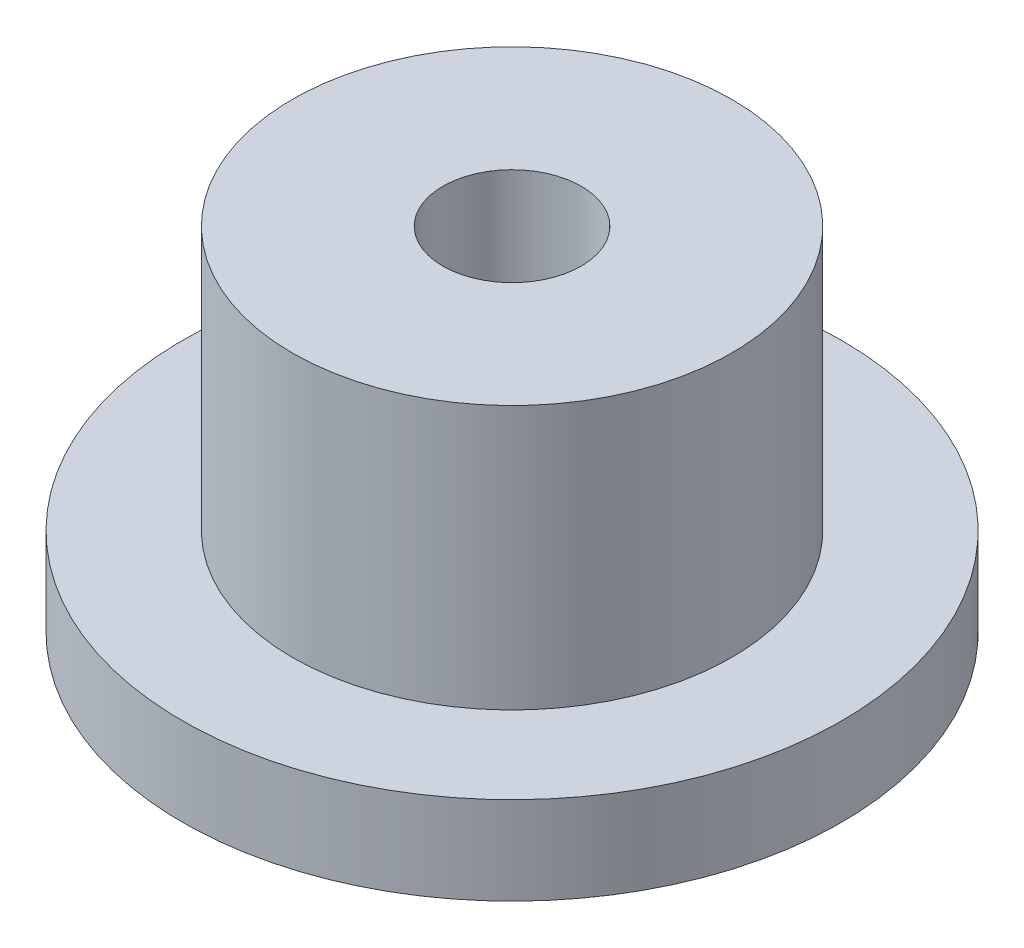
SolidWorks part; units mm, degrees
material "Alum Plate"
ref_plane "Front Plane" through (0, 0, 0) normal (0, 0, 1) x (1, 0, 0)
ref_plane "Top Plane" through (0, 0, 0) normal (0, 1, 0) x (1, 0, 0)
ref_plane "Right Plane" through (0, 0, 0) normal (1, 0, 0) x (0, 0, -1)
other "Bounding Box"
ref_plane "Default Plane" through (-8.9266, -12.7485, 0) normal (-0.1736, 0.9848, 0) x (0.9848, 0.1736, 0)
sketch "Sketch2" plane through (0, 0, 0) normal (1, 0, 0) x (0, 0, -1)
  line L0 (-9.525, 2.54) -> (-9.525, -2.54) construction
  line L1 (-6.35, 2.54) -> (-6.35, 5.08)
  line L2 (-9.525, -2.54) -> (-6.35, -2.54)
  line L3 (-6.35, -2.54) -> (-6.35, 2.54)
  line L4 (-6.35, 2.54) -> (-9.525, 2.54) construction
  line L5 (-6.35, 0) -> (-9.525, 0) construction
  line L6 (-9.525, 2.54) -> (-9.525, 5.08) construction
  line L7 (-9.525, 5.08) -> (-6.35, 5.08) construction
  line L8 (0, 0) -> (0, 5.08)
  line L9 (-6.35, 5.08) -> (0, 5.08)
  line L10 (0, 0) -> (0, -5.08)
  line L11 (0, -5.08) -> (-9.525, -5.08)
  line L12 (-9.525, -5.08) -> (-9.525, -2.54)
  dimension "D1" = 3.175
  dimension "D2" = 6.35
  dimension "D3" = 7.62
  dimension "D4" = 10.16
revolve "Revolve1" add sketch "Sketch2" angle 360 about L8
sketch "Sketch3" plane through (0, 5.08, 0) normal (0, 1, 0) x (1, 0, 0)
  circle A0 centre (0, 0) radius 2
  dimension "D1" = 4
extrude "Cut-Extrude1" cut sketch "Sketch3" against normal through all
